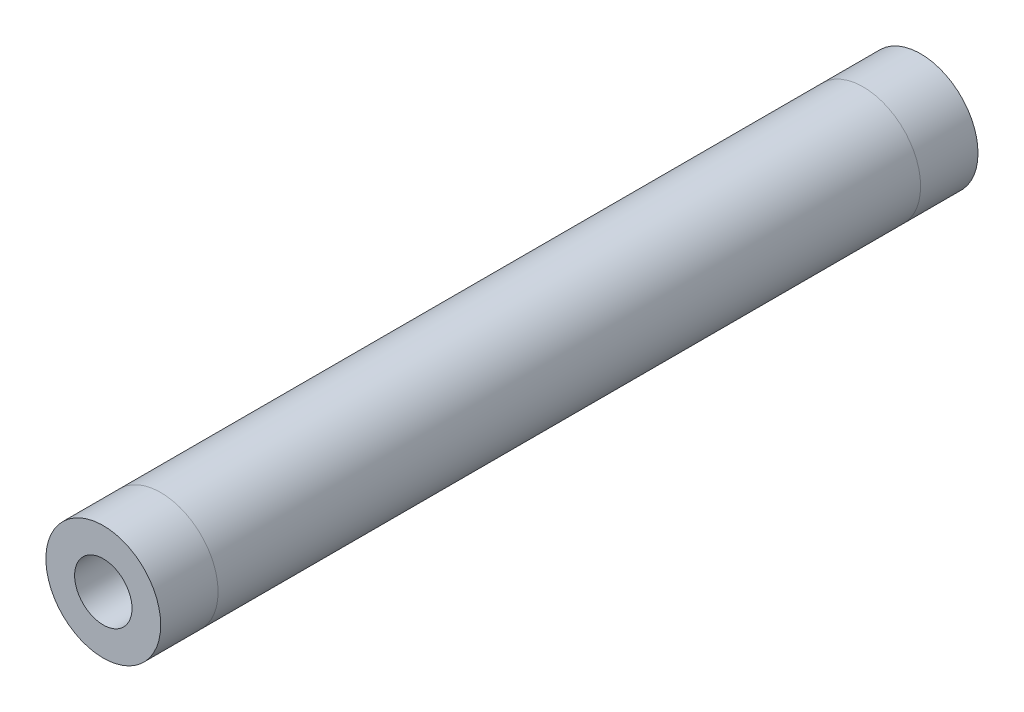
SolidWorks part; units mm, degrees
material "AISI 4130 Steel, normalized at 870C"
ref_plane "Front Plane" through (0, 0, 0) normal (0, 0, 1) x (1, 0, 0)
ref_plane "Top Plane" through (0, 0, 0) normal (0, 1, 0) x (1, 0, 0)
ref_plane "Right Plane" through (0, 0, 0) normal (1, 0, 0) x (0, 0, -1)
sketch "Axis" plane through (0, 0, 0) normal (0, 1, 0) x (1, 0, 0)
  line L0 (0, 0) -> (0, 21.9075) construction
  line L1 (0, 21.9075) -> (0, 112.3282) construction
  line L2 (0, 112.3282) -> (0, 134.2357) construction
  dimension "D1" = 21.9075
  dimension "D2" = 134.2357
sketch "Sketch2" plane through (0, 0, 0) normal (0, 0, 1) x (1, 0, 0)
  circle A0 centre (0, 0) radius 6.35
  circle A1 centre (0, 0) radius 3.175
  circle A2 centre (0, 0) radius 4.7625
  dimension "D1" = 12.7
  dimension "D2" = 6.35
  dimension "D3" = 9.525
extrude "Threaded Insert 1-1" add sketch "Sketch2" against normal blind 6.35 from vertex contours A0 A2 | A2 A1 region at (-6.1704, 0, 0) region at (-4.6278, 0, 0) starting at point (0, 0, -21.9075)
extrude "Threaded Insert 1-2" add sketch "Sketch2<5>" against normal blind 6.35 from surface contours A2 A1 region at (-4.6278, 0, 0) starting at face at (6.35, 0, -28.2575)
sketch "Sketch2<5>" plane through (0, 0, 0) normal (0, 0, 1) x (1, 0, 0) same geometry as "Sketch2"
extrude "Boss-Extrude4" add sketch "Sketch2<7>" along normal blind 6.35 from vertex separate body contours A0 A2 | A2 A1 region at (-6.1704, 0, 0) region at (-4.6278, 0, 0) starting at point (0, 0, -112.3282)
sketch "Sketch2<7>" plane through (0, 0, 0) normal (0, 0, 1) x (1, 0, 0) same geometry as "Sketch2"
extrude "Boss-Extrude5" add sketch "Sketch2<8>" along normal blind 6.35 from surface contours A2 A1 region at (-4.6278, 0, 0) starting at face at (6.35, 0, -105.9782)
sketch "Sketch2<8>" plane through (0, 0, 0) normal (0, 0, 1) x (1, 0, 0) same geometry as "Sketch2"
extrude "Boss-Extrude6" add sketch "Sketch2<9>" against normal up to surface (105.9782 mm away) from surface separate body contours A0 A2 region at (-6.1704, 0, 0) up to face at (6.35, 0, -105.9782) starting at face at (4.7625, 0, -28.2575)
sketch "Sketch2<9>" plane through (0, 0, 0) normal (0, 0, 1) x (1, 0, 0) same geometry as "Sketch2"
equation "\"Tube Outer Diameter\"= .5"
equation "\"Tube Inner Diameter\"= .375"
equation "\"Rod end Diameter\"= .25"
equation "\"Threaded Insert Out\"= .25"
equation "\"Threaded Insert In\"= .25'`"
equation "\"D1@Sketch2\"=\"Tube Outer Diameter\""
equation "\"D2@Sketch2\"=\"Rod end Diameter\""
equation "\"D1@Threaded Insert 1-1\" = \"Threaded Insert Out\""
equation "\"D3@Sketch2\"=\"Tube Inner Diameter\""
equation "\"D1@Threaded Insert 1-2\" = \"Threaded Insert In\""
equation "\"D1@Boss-Extrude4\"=\"Threaded Insert Out\""
equation "\"D1@Boss-Extrude5\"=\"Threaded Insert In\""
